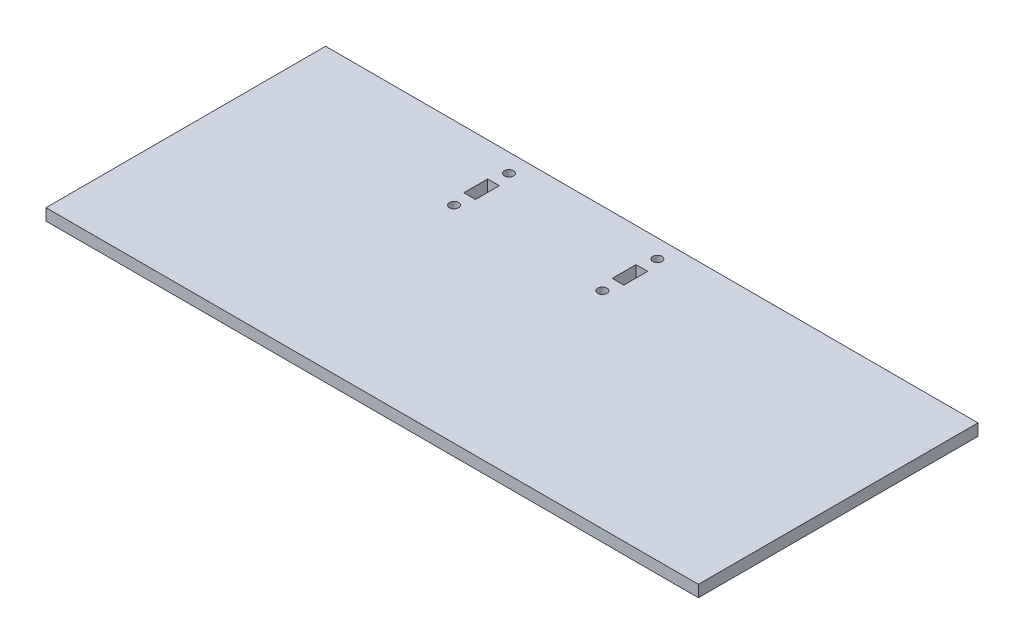
SolidWorks part; units mm, degrees
ref_plane "Front Plane" through (0, 0, 0) normal (0, 0, 1) x (1, 0, 0)
ref_plane "Top Plane" through (0, 0, 0) normal (0, 1, 0) x (1, 0, 0)
ref_plane "Right Plane" through (0, 0, 0) normal (1, 0, 0) x (0, 0, -1)
sketch "Sketch1" plane through (0, 0, 0) normal (0, 1, 0) x (1, 0, 0)
  line L0 (150.43, 152.4) -> (150.43, 0) construction
  line L1 (0, 0) -> (355.6, 0)
  line L2 (0, 0) -> (0, 152.4)
  line L3 (0, 152.4) -> (355.6, 152.4)
  line L4 (355.6, 0) -> (355.6, 152.4)
  line L5 (106.825, 133.9) -> (113.175, 133.9)
  line L6 (106.825, 133.9) -> (106.825, 120.9)
  line L7 (106.825, 120.9) -> (113.175, 120.9)
  line L8 (113.175, 133.9) -> (113.175, 120.9)
  line L9 (187.685, 133.9) -> (194.035, 133.9)
  line L10 (187.685, 133.9) -> (187.685, 120.9)
  line L11 (187.685, 120.9) -> (194.035, 120.9)
  line L12 (194.035, 133.9) -> (194.035, 120.9)
  line L13 (110, 152.4) -> (110, 0) construction
  line L14 (190.86, 152.4) -> (190.86, 0) construction
  line L15 (110, 142.4) -> (190.86, 142.4) construction
  line L16 (110, 112.4) -> (190.86, 112.4) construction
  line L17 (106.825, 127.4) -> (194.035, 127.4) construction
  circle A0 centre (110, 142.4) radius 2.4892
  circle A1 centre (190.86, 142.4) radius 2.4892
  circle A2 centre (110, 112.4) radius 2.4892
  circle A3 centre (190.86, 112.4) radius 2.4892
  point P27 (150.43, 142.4)
  point P28 (150.43, 112.4)
  point P31 (150.43, 127.4)
  point P32 (110, 120.9)
  dimension "D6" = 4.9784
  dimension "D1" = 355.6
  dimension "D2" = 152.4
  dimension "D3" = 13
  dimension "D4" = 6.35
  dimension "D5" = 30
  dimension "D7" = 15
  dimension "D8" = 80.86
  dimension "D9" = 110
  dimension "D10" = 10
extrude "Boss-Extrude1" add sketch "Sketch1" along normal blind 6.35
